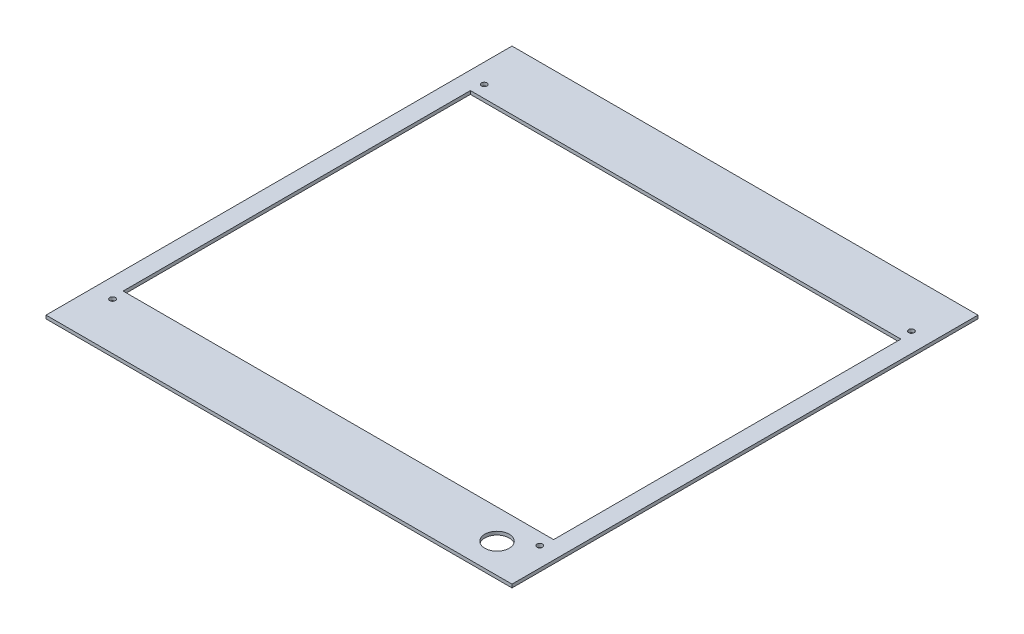
SolidWorks part; units mm, degrees
ref_plane "Front Plane" through (0, 0, 0) normal (0, 0, 1) x (1, 0, 0)
ref_plane "Top Plane" through (0, 0, 0) normal (0, 1, 0) x (1, 0, 0)
ref_plane "Right Plane" through (0, 0, 0) normal (1, 0, 0) x (0, 0, -1)
sketch "Sketch1" plane through (0, 0, 0) normal (0, 1, 0) x (1, 0, 0)
  line L1 (-210, -210) -> (210, -210)
  line L2 (-210, -210) -> (-210, 210)
  line L3 (-210, 210) -> (210, 210)
  line L4 (210, -210) -> (210, 210)
  line L5 (-210, -210) -> (210, 210) construction
  line L6 (-210, 210) -> (210, -210) construction
  line L7 (-194, 156.5) -> (194, 156.5)
  line L8 (-194, 156.5) -> (-194, -156.5)
  line L9 (-194, -156.5) -> (194, -156.5)
  line L10 (194, 156.5) -> (194, -156.5)
  line L11 (-194, 156.5) -> (194, -156.5) construction
  line L12 (-194, -156.5) -> (194, 156.5) construction
  circle A0 centre (169.75, -183.25) radius 11
  arc A1 (-192.5, -170) -> (-195, -167.5) centre (-192.5, -167.5) ccw construction
  arc A2 (-192.5, -170) -> (-195, -167.5) centre (-192.5, -167.5) ccw
  arc A3 (-195, -167.5) -> (-192.5, -170) centre (-192.5, -167.5) ccw construction
  arc A4 (-195, -167.5) -> (-192.5, -170) centre (-192.5, -167.5) ccw
  arc A5 (192.5, -165) -> (195, -167.5) centre (192.5, -167.5) ccw construction
  arc A6 (192.5, -165) -> (195, -167.5) centre (192.5, -167.5) ccw
  arc A7 (195, -167.5) -> (192.5, -165) centre (192.5, -167.5) ccw construction
  arc A8 (195, -167.5) -> (192.5, -165) centre (192.5, -167.5) ccw
  arc A9 (195, 167.5) -> (192.5, 170) centre (192.5, 167.5) ccw construction
  arc A10 (192.5, 170) -> (195, 167.5) centre (192.5, 167.5) ccw construction
  arc A11 (195, 167.5) -> (192.5, 170) centre (192.5, 167.5) ccw
  arc A12 (192.5, 170) -> (195, 167.5) centre (192.5, 167.5) ccw
  arc A13 (-195, 167.5) -> (-192.5, 165) centre (-192.5, 167.5) ccw construction
  arc A14 (-192.5, 165) -> (-195, 167.5) centre (-192.5, 167.5) ccw construction
  arc A15 (-195, 167.5) -> (-192.5, 165) centre (-192.5, 167.5) ccw
  arc A16 (-192.5, 165) -> (-195, 167.5) centre (-192.5, 167.5) ccw
  point P0 (0, 0)
  point P5 (0, 0)
  dimension "D5" = 22
  dimension "D1" = 420
  dimension "D2" = 420
  dimension "D3" = 313
  dimension "D4" = 388
extrude "Boss-Extrude1" add sketch "Sketch1" along normal blind 3
